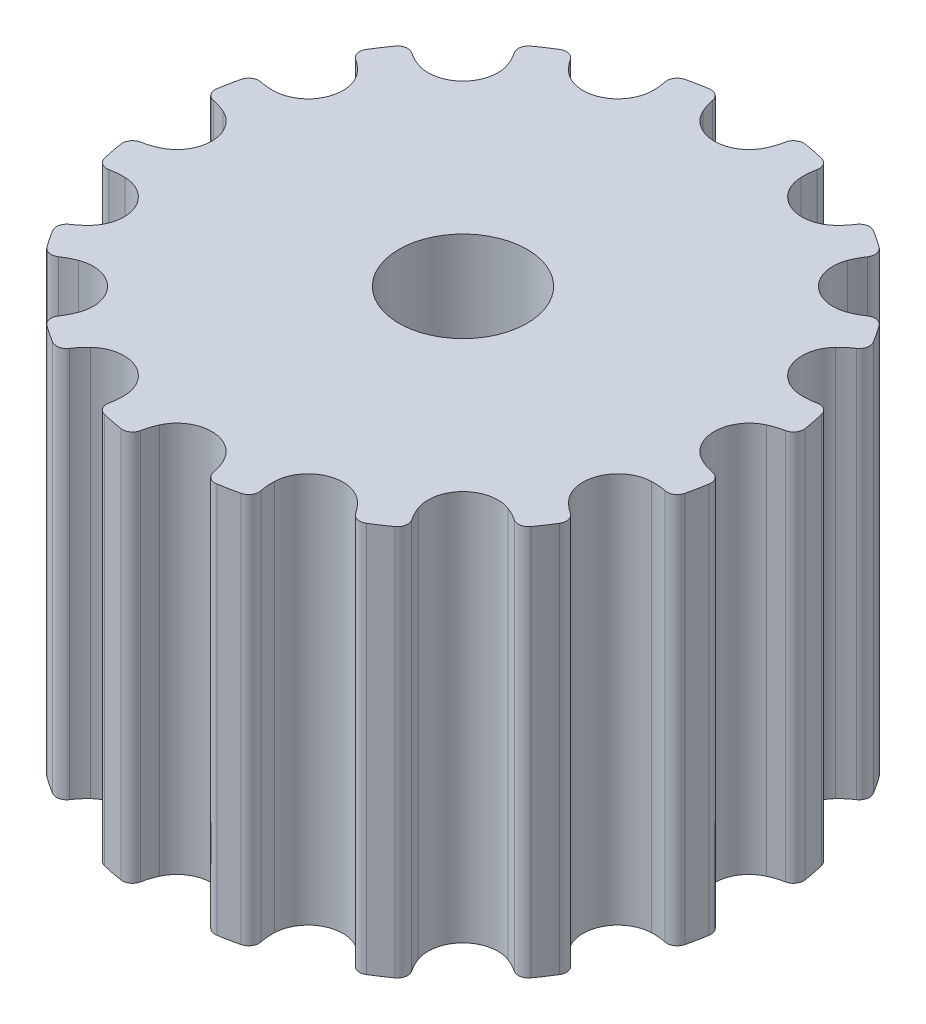
SolidWorks part; units mm, degrees
material "Alum Plate"
ref_plane "Front Plane" through (0, 0, 0) normal (0, 0, 1) x (1, 0, 0)
ref_plane "Top Plane" through (0, 0, 0) normal (0, 1, 0) x (1, 0, 0)
ref_plane "Right Plane" through (0, 0, 0) normal (1, 0, 0) x (0, 0, -1)
other "Bounding Box"
ref_plane "Default Plane" through (-8.9266, -12.7485, 0) normal (-0.1736, 0.9848, 0) x (0.9848, 0.1736, 0)
sketch "Sketch1" plane through (0, 0, 0) normal (0, 1, 0) x (1, 0, 0)
  line L0 (0, -7.8245) -> (0, 0) construction
  circle A0 centre (0, 0) radius 1.5625
  arc B0 (-1.8508, -6.777) -> (-1.6633, -7.0715) centre (-1.6061, -6.8282) ccw
  arc B1 (-1.6633, -7.0715) -> (-1.1695, -7.1697) centre (0, 0) ccw
  arc B2 (-1.1695, -7.1697) -> (-0.8836, -6.9694) centre (-1.1292, -6.923) ccw
  arc B3 (-0.7739, -6.6229) -> (-0.8836, -6.9694) centre (0.61, -7.2516) ccw
  arc B4 (0.7739, -6.6229) -> (-0.7739, -6.6229) centre (0, -6.9745) ccw
  arc B5 (0.8836, -6.9694) -> (0.7739, -6.6229) centre (-0.61, -7.2516) ccw
  arc B6 (0.8836, -6.9694) -> (1.1695, -7.1697) centre (1.1292, -6.923) ccw
  arc B7 (1.1695, -7.1697) -> (1.6633, -7.0715) centre (0, 0) ccw
  arc B8 (1.6633, -7.0715) -> (1.8508, -6.777) centre (1.6061, -6.8282) ccw
  arc B9 (1.8195, -6.4149) -> (1.8508, -6.777) centre (3.3386, -6.4662) ccw
  arc B10 (3.2495, -5.8226) -> (1.8195, -6.4149) centre (2.669, -6.4436) ccw
  arc B11 (3.4834, -6.1008) -> (3.2495, -5.8226) centre (2.2115, -6.9331) ccw
  arc B12 (3.4834, -6.1008) -> (3.8242, -6.1764) centre (3.6926, -5.9639) ccw
  arc B13 (3.8242, -6.1764) -> (4.2428, -5.8967) centre (0, 0) ccw
  arc B14 (4.2428, -5.8967) -> (4.3033, -5.5529) centre (4.0968, -5.6938) ccw
  arc B15 (4.1359, -5.2303) -> (4.3033, -5.5529) centre (5.559, -4.6963) ccw
  arc B16 (5.2303, -4.1359) -> (4.1359, -5.2303) centre (4.9317, -4.9317) ccw
  arc B17 (5.5529, -4.3033) -> (5.2303, -4.1359) centre (4.6963, -5.559) ccw
  arc B18 (5.5529, -4.3033) -> (5.8967, -4.2428) centre (5.6938, -4.0968) ccw
  arc B19 (5.8967, -4.2428) -> (6.1764, -3.8242) centre (0, 0) ccw
  arc B20 (6.1764, -3.8242) -> (6.1008, -3.4834) centre (5.9639, -3.6926) ccw
  arc B21 (5.8226, -3.2495) -> (6.1008, -3.4834) centre (6.9331, -2.2115) ccw
  arc B22 (6.4149, -1.8195) -> (5.8226, -3.2495) centre (6.4436, -2.669) ccw
  arc B23 (6.777, -1.8508) -> (6.4149, -1.8195) centre (6.4662, -3.3386) ccw
  arc B24 (6.777, -1.8508) -> (7.0715, -1.6633) centre (6.8282, -1.6061) ccw
  arc B25 (7.0715, -1.6633) -> (7.1697, -1.1695) centre (0, 0) ccw
  arc B26 (7.1697, -1.1695) -> (6.9694, -0.8836) centre (6.923, -1.1292) ccw
  arc B27 (6.6229, -0.7739) -> (6.9694, -0.8836) centre (7.2516, 0.61) ccw
  arc B28 (6.6229, 0.7739) -> (6.6229, -0.7739) centre (6.9745, 0) ccw
  arc B29 (6.9694, 0.8836) -> (6.6229, 0.7739) centre (7.2516, -0.61) ccw
  arc B30 (6.9694, 0.8836) -> (7.1697, 1.1695) centre (6.923, 1.1292) ccw
  arc B31 (7.1697, 1.1695) -> (7.0715, 1.6633) centre (0, 0) ccw
  arc B32 (7.0715, 1.6633) -> (6.777, 1.8508) centre (6.8282, 1.6061) ccw
  arc B33 (6.4149, 1.8195) -> (6.777, 1.8508) centre (6.4662, 3.3386) ccw
  arc B34 (5.8226, 3.2495) -> (6.4149, 1.8195) centre (6.4436, 2.669) ccw
  arc B35 (6.1008, 3.4834) -> (5.8226, 3.2495) centre (6.9331, 2.2115) ccw
  arc B36 (6.1008, 3.4834) -> (6.1764, 3.8242) centre (5.9639, 3.6926) ccw
  arc B37 (6.1764, 3.8242) -> (5.8967, 4.2428) centre (0, 0) ccw
  arc B38 (5.8967, 4.2428) -> (5.5529, 4.3033) centre (5.6938, 4.0968) ccw
  arc B39 (5.2303, 4.1359) -> (5.5529, 4.3033) centre (4.6963, 5.559) ccw
  arc B40 (4.1359, 5.2303) -> (5.2303, 4.1359) centre (4.9317, 4.9317) ccw
  arc B41 (4.3033, 5.5529) -> (4.1359, 5.2303) centre (5.559, 4.6963) ccw
  arc B42 (4.3033, 5.5529) -> (4.2428, 5.8967) centre (4.0968, 5.6938) ccw
  arc B43 (4.2428, 5.8967) -> (3.8242, 6.1764) centre (0, 0) ccw
  arc B44 (3.8242, 6.1764) -> (3.4834, 6.1008) centre (3.6926, 5.9639) ccw
  arc B45 (3.2495, 5.8226) -> (3.4834, 6.1008) centre (2.2115, 6.9331) ccw
  arc B46 (1.8195, 6.4149) -> (3.2495, 5.8226) centre (2.669, 6.4436) ccw
  arc B47 (1.8508, 6.777) -> (1.8195, 6.4149) centre (3.3386, 6.4662) ccw
  arc B48 (1.8508, 6.777) -> (1.6633, 7.0715) centre (1.6061, 6.8282) ccw
  arc B49 (1.6633, 7.0715) -> (1.1695, 7.1697) centre (0, 0) ccw
  arc B50 (1.1695, 7.1697) -> (0.8836, 6.9694) centre (1.1292, 6.923) ccw
  arc B51 (0.7739, 6.6229) -> (0.8836, 6.9694) centre (-0.61, 7.2516) ccw
  arc B52 (-0.7739, 6.6229) -> (0.7739, 6.6229) centre (0, 6.9745) ccw
  arc B53 (-0.8836, 6.9694) -> (-0.7739, 6.6229) centre (0.61, 7.2516) ccw
  arc B54 (-0.8836, 6.9694) -> (-1.1695, 7.1697) centre (-1.1292, 6.923) ccw
  arc B55 (-1.1695, 7.1697) -> (-1.6633, 7.0715) centre (0, 0) ccw
  arc B56 (-1.6633, 7.0715) -> (-1.8508, 6.777) centre (-1.6061, 6.8282) ccw
  arc B57 (-1.8195, 6.4149) -> (-1.8508, 6.777) centre (-3.3386, 6.4662) ccw
  arc B58 (-3.2495, 5.8226) -> (-1.8195, 6.4149) centre (-2.669, 6.4436) ccw
  arc B59 (-3.4834, 6.1008) -> (-3.2495, 5.8226) centre (-2.2115, 6.9331) ccw
  arc B60 (-3.4834, 6.1008) -> (-3.8242, 6.1764) centre (-3.6926, 5.9639) ccw
  arc B61 (-3.8242, 6.1764) -> (-4.2428, 5.8967) centre (0, 0) ccw
  arc B62 (-4.2428, 5.8967) -> (-4.3033, 5.5529) centre (-4.0968, 5.6938) ccw
  arc B63 (-4.1359, 5.2303) -> (-4.3033, 5.5529) centre (-5.559, 4.6963) ccw
  arc B64 (-5.2303, 4.1359) -> (-4.1359, 5.2303) centre (-4.9317, 4.9317) ccw
  arc B65 (-5.5529, 4.3033) -> (-5.2303, 4.1359) centre (-4.6963, 5.559) ccw
  arc B66 (-5.5529, 4.3033) -> (-5.8967, 4.2428) centre (-5.6938, 4.0968) ccw
  arc B67 (-5.8967, 4.2428) -> (-6.1764, 3.8242) centre (0, 0) ccw
  arc B68 (-6.1764, 3.8242) -> (-6.1008, 3.4834) centre (-5.9639, 3.6926) ccw
  arc B69 (-5.8226, 3.2495) -> (-6.1008, 3.4834) centre (-6.9331, 2.2115) ccw
  arc B70 (-6.4149, 1.8195) -> (-5.8226, 3.2495) centre (-6.4436, 2.669) ccw
  arc B71 (-6.777, 1.8508) -> (-6.4149, 1.8195) centre (-6.4662, 3.3386) ccw
  arc B72 (-6.777, 1.8508) -> (-7.0715, 1.6633) centre (-6.8282, 1.6061) ccw
  arc B73 (-7.0715, 1.6633) -> (-7.1697, 1.1695) centre (0, 0) ccw
  arc B74 (-7.1697, 1.1695) -> (-6.9694, 0.8836) centre (-6.923, 1.1292) ccw
  arc B75 (-6.6229, 0.7739) -> (-6.9694, 0.8836) centre (-7.2516, -0.61) ccw
  arc B76 (-6.6229, -0.7739) -> (-6.6229, 0.7739) centre (-6.9745, 0) ccw
  arc B77 (-6.9694, -0.8836) -> (-6.6229, -0.7739) centre (-7.2516, 0.61) ccw
  arc B78 (-6.9694, -0.8836) -> (-7.1697, -1.1695) centre (-6.923, -1.1292) ccw
  arc B79 (-7.1697, -1.1695) -> (-7.0715, -1.6633) centre (0, 0) ccw
  arc B80 (-7.0715, -1.6633) -> (-6.777, -1.8508) centre (-6.8282, -1.6061) ccw
  arc B81 (-6.4149, -1.8195) -> (-6.777, -1.8508) centre (-6.4662, -3.3386) ccw
  arc B82 (-5.8226, -3.2495) -> (-6.4149, -1.8195) centre (-6.4436, -2.669) ccw
  arc B83 (-6.1008, -3.4834) -> (-5.8226, -3.2495) centre (-6.9331, -2.2115) ccw
  arc B84 (-6.1008, -3.4834) -> (-6.1764, -3.8242) centre (-5.9639, -3.6926) ccw
  arc B85 (-6.1764, -3.8242) -> (-5.8967, -4.2428) centre (0, 0) ccw
  arc B86 (-5.8967, -4.2428) -> (-5.5529, -4.3033) centre (-5.6938, -4.0968) ccw
  arc B87 (-5.2303, -4.1359) -> (-5.5529, -4.3033) centre (-4.6963, -5.559) ccw
  arc B88 (-4.1359, -5.2303) -> (-5.2303, -4.1359) centre (-4.9317, -4.9317) ccw
  arc B89 (-4.3033, -5.5529) -> (-4.1359, -5.2303) centre (-5.559, -4.6963) ccw
  arc B90 (-4.3033, -5.5529) -> (-4.2428, -5.8967) centre (-4.0968, -5.6938) ccw
  arc B91 (-4.2428, -5.8967) -> (-3.8242, -6.1764) centre (0, 0) ccw
  arc B92 (-3.8242, -6.1764) -> (-3.4834, -6.1008) centre (-3.6926, -5.9639) ccw
  arc B93 (-3.2495, -5.8226) -> (-3.4834, -6.1008) centre (-2.2115, -6.9331) ccw
  arc B94 (-1.8195, -6.4149) -> (-3.2495, -5.8226) centre (-2.669, -6.4436) ccw
  arc B95 (-1.8508, -6.777) -> (-1.8195, -6.4149) centre (-3.3386, -6.4662) ccw
  dimension "D1" = 3.125
sketch_block_instance "Block-GT2 16 Tooth Profile-1"
sketch_block "Block-GT2 16 Tooth Profile"
extrude "Boss-Extrude1" add sketch "Sketch1" along normal mid plane 9.525
